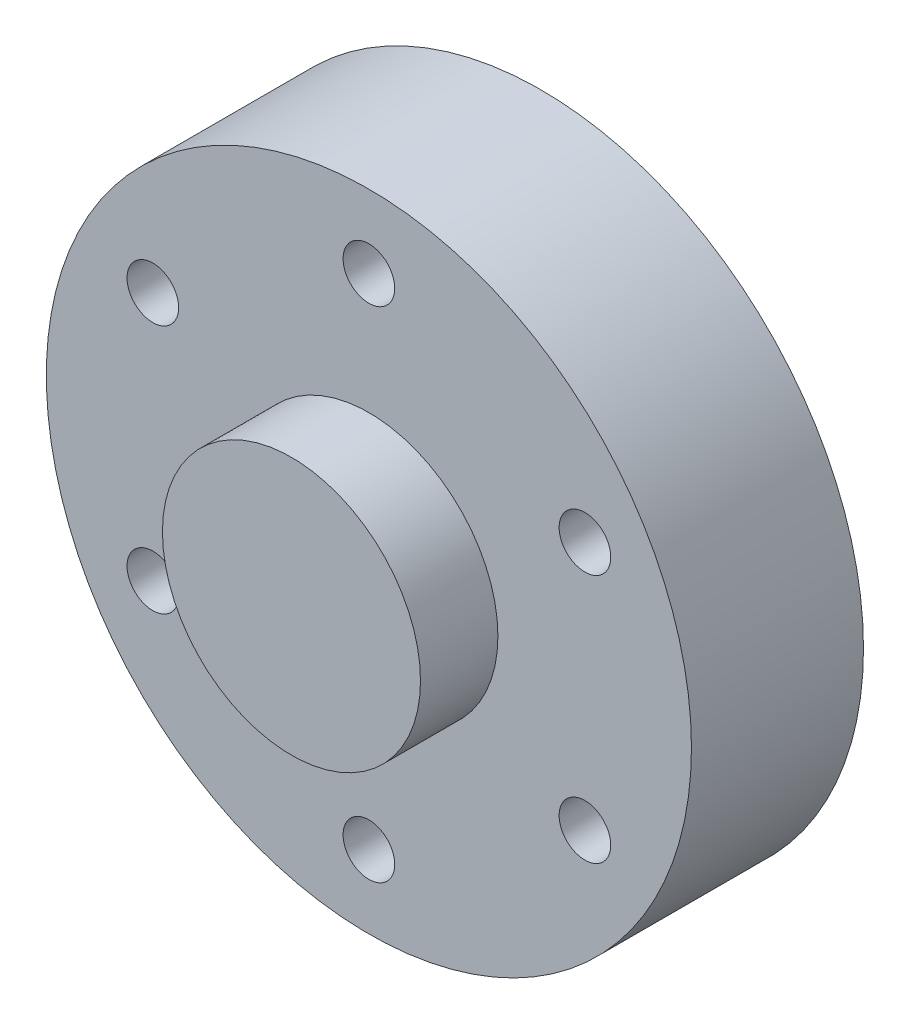
SolidWorks part; units mm, degrees
ref_plane "Front Plane" through (0, 0, 0) normal (0, 0, 1) x (1, 0, 0)
ref_plane "Top Plane" through (0, 0, 0) normal (0, 1, 0) x (1, 0, 0)
ref_plane "Right Plane" through (0, 0, 0) normal (1, 0, 0) x (0, 0, -1)
sketch "Sketch2" plane through (0, 0, 0) normal (0, 0, 1) x (1, 0, 0)
  circle A0 centre (0, 0) radius 9.5
  circle A1 centre (0, 0) radius 14.5 construction
  circle A3 centre (0, 0) radius 18.75
  circle A4 centre (0, 14.5) radius 1.5
  circle A5 centre (12.5574, 7.25) radius 1.5
  circle A6 centre (12.5574, -7.25) radius 1.5
  circle A7 centre (0, -14.5) radius 1.5
  circle A8 centre (-12.5574, -7.25) radius 1.5
  circle A9 centre (-12.5574, 7.25) radius 1.5
  point P21 (0, 0)
  dimension "D1" = 19
  dimension "D3" = 29
  dimension "D4" = 37.5
  dimension "D5" = 3
  dimension "D6" = 6
extrude "Boss-Extrude1" add sketch "Sketch2" along normal blind 10 contours A3 A9 A8 A7 A6 A5 A4 A0 | A0 region at (0, 0, 0) region at (-18.2197, 0, 0)
sketch "Sketch3" plane through (0, 0, 10) normal (0, 0, 1) x (1, 0, 0)
  circle A0 centre (0, 0) radius 7.5
  dimension "D1" = 15
extrude "Boss-Extrude2" add sketch "Sketch3" along normal blind 4.5
sketch "Sketch6" plane through (0, 0, 0) normal (0, 0, -1) x (-1, 0, 0)
  circle A0 centre (0, 0) radius 7.5
  dimension "D1" = 15
extrude "Boss-Extrude4" add sketch "Sketch6" along normal blind 4.5 contours A0
sketch "Sketch7" plane through (0, 0, -4.5) normal (0, 0, -1) x (-1, 0, 0)
  circle A0 centre (0, 0) radius 2
  dimension "D1" = 4
extrude "Boss-Extrude5" add sketch "Sketch7" along normal blind 1
fillet "Fillet2" radius 0.05 1 edges at (-2, 0, -5.5)
sketch "Sketch9" plane through (0, 0, -5.5) normal (0, 0, -1) x (-1, 0, 0)
  line L1 (-0.8281, 1.2507) -> (0.8281, 1.2507)
  arc A0 (-0.8281, 1.2507) -> (0.8281, 1.2507) centre (0, 0) ccw
  dimension "D1" = 3
extrude "Cut-Extrude1" cut sketch "Sketch9" against normal blind 11
